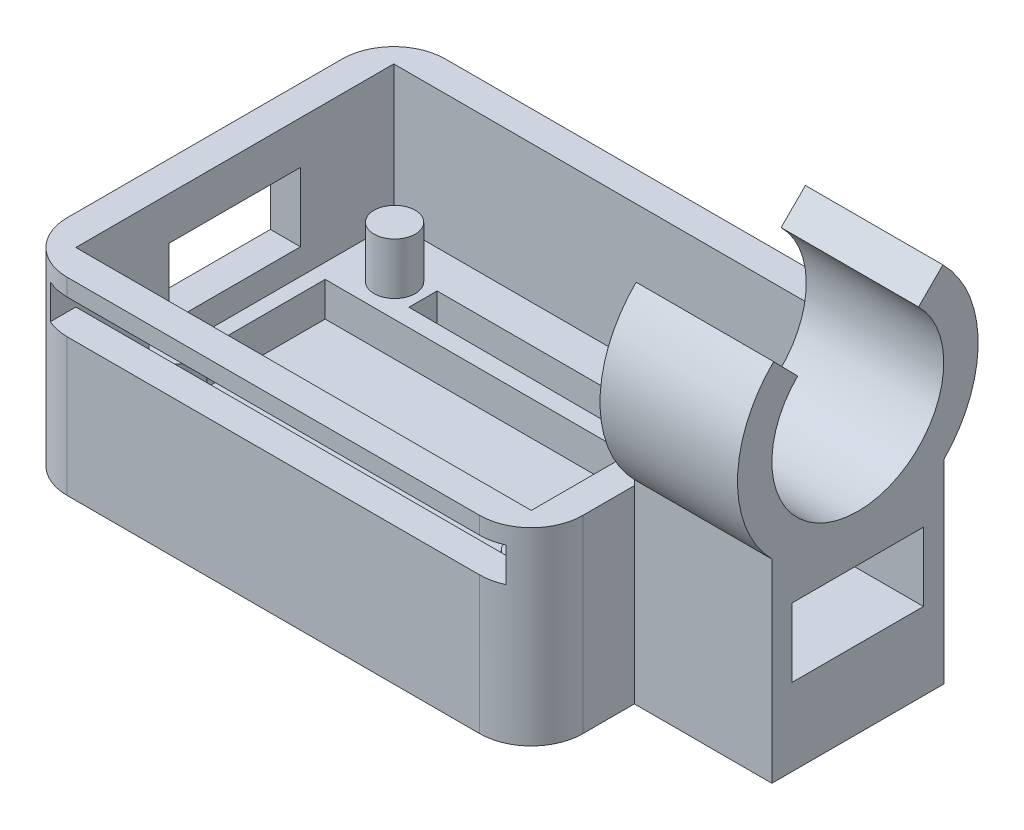
SolidWorks part; units mm, degrees
ref_plane "Front Plane" through (0, 0, 0) normal (0, 0, 1) x (1, 0, 0)
ref_plane "Top Plane" through (0, 0, 0) normal (0, 1, 0) x (1, 0, 0)
ref_plane "Right Plane" through (0, 0, 0) normal (1, 0, 0) x (0, 0, -1)
sketch "Sketch1" plane through (0, 0, 0) normal (0, 1, 0) x (1, 0, 0)
  line L1 (-15, -11) -> (15, -11)
  line L2 (-15, -11) -> (-15, 11)
  line L3 (-15, 11) -> (15, 11)
  line L4 (15, -11) -> (15, 11)
  line L5 (-15, -11) -> (15, 11) construction
  line L6 (-15, 11) -> (15, -11) construction
  point P0 (0, 0)
  dimension "D1" = 30
  dimension "D2" = 22
extrude "Boss-Extrude1" add sketch "Sketch1" along normal blind 11
sketch "Sketch2" plane through (0, 11, 0) normal (0, 1, 0) x (1, 0, 0)
  line L1 (-13.25, -9.25) -> (13.25, -9.25)
  line L2 (-13.25, -9.25) -> (-13.25, 9.25)
  line L3 (-13.25, 9.25) -> (13.25, 9.25)
  line L4 (13.25, -9.25) -> (13.25, 9.25)
  line L5 (-13.25, -9.25) -> (13.25, 9.25) construction
  line L6 (-13.25, 9.25) -> (13.25, -9.25) construction
  point P0 (0, 0)
  dimension "D1" = 26.5
  dimension "D2" = 18.5
extrude "Cut-Extrude1" cut sketch "Sketch2" against normal blind 8
sketch "Sketch3" plane through (0, 3, 0) normal (0, 1, 0) x (1, 0, 0)
  line L0 (-10.25, 6.3) -> (-10.25, 9.25) construction
  line L1 (-13.25, -6.3) -> (-10.25, -6.3) construction
  line L2 (-13.25, 9.25) -> (-13.25, -9.25) construction
  line L3 (-10.25, -6.3) -> (-10.25, -9.25) construction
  line L4 (-13.25, -9.25) -> (13.25, -9.25) construction
  line L5 (0, -6.05) -> (0, 6.05) construction
  line L6 (-6.05, 0) -> (6.05, 0) construction
  line L7 (13.25, 9.25) -> (-13.25, 9.25) construction
  line L8 (10.25, 6.3) -> (10.25, 9.25) construction
  line L9 (10.25, -6.3) -> (10.25, -9.25) construction
  line L10 (-13.25, -9.25) -> (13.25, -9.25) construction
  circle A1 centre (-10.25, -6.3) radius 1.2
  circle A2 centre (10.25, -6.3) radius 1.2
  circle A3 centre (10.25, 6.3) radius 1.2
  circle A5 centre (-10.25, 6.3) radius 1.2
  dimension "D3" = 2.4
  dimension "D4" = 2.4
  dimension "D1" = 3
  dimension "D2" = 2.95
  dimension "D5" = 2.95
extrude "Boss-Extrude2" add sketch "Sketch3" along normal blind 3
sketch "Sketch4" plane through (0, 3, 0) normal (0, 1, 0) x (1, 0, 0)
  line L5 (8.5527, 7.0707) -> (8.5527, 5.3672)
  line L6 (-9.05, 6.25) -> (-8.55, 6.25) construction
  line L7 (9.0527, 6.219) -> (8.5527, 6.219) construction
  line L10 (-8.55, 5.4293) -> (-8.55, 7.0707)
  line L11 (-8.55, 7.0707) -> (8.5527, 7.0707)
  line L12 (8.5527, 5.3672) -> (-8.55, 5.4293)
  circle A6 centre (10.25, 6.3) radius 1.2 construction
  circle A7 centre (10.25, 6.3) radius 1.2 construction
  point P17 (-8.55, 6.25)
  dimension "D1" = 0.5
  dimension "D2" = 0.5
extrude "Cut-Extrude2" cut sketch "Sketch4" against normal blind 2
mirror "Mirror1" about plane through (0, 0, 0) normal (0, 0, 1) of "Cut-Extrude2"
sketch "Sketch5" plane through (-15, 0, 0) normal (-1, 0, 0) x (0, 0, 1)
  line L0 (0, 3) -> (0, 4.5) construction
  line L1 (-9.25, 3) -> (9.25, 3) construction
  line L2 (-3.8195, 4.5) -> (3.8195, 4.5)
  line L3 (-3.8195, 4.5) -> (-3.8195, 8.5)
  line L4 (-3.8195, 8.5) -> (3.8195, 8.5)
  line L5 (3.8195, 8.5) -> (3.8195, 4.5)
  point P8 (0, 4.5)
  dimension "D1" = 4
  dimension "D2" = 1.5
extrude "Cut-Extrude3" cut sketch "Sketch5" against normal through all
sketch "Sketch6" plane through (0, 0, 11) normal (0, 0, 1) x (1, 0, 0)
  line L0 (0, 11) -> (0, 10) construction
  line L1 (-15, 11) -> (15, 11) construction
  line L2 (-13.25, 3) -> (-13.25, 11) construction
  line L3 (-13.25, 10) -> (13.25, 10)
  line L4 (-13.25, 10) -> (-13.25, 8)
  line L5 (-13.25, 8) -> (13.25, 8)
  line L6 (13.25, 10) -> (13.25, 8)
  line L7 (13.25, 3) -> (13.25, 11) construction
  dimension "D1" = 1
  dimension "D2" = 2
extrude "Cut-Extrude4" cut sketch "Sketch6" against normal up to next
sketch "Sketch8" plane through (0, 3, 0) normal (0, 1, 0) x (1, 0, 0)
  line L1 (-12.3879, -4.3961) -> (12.3879, -4.3961)
  line L2 (-12.3879, -4.3961) -> (-12.3879, 4.3961)
  line L3 (-12.3879, 4.3961) -> (12.3879, 4.3961)
  line L4 (12.3879, -4.3961) -> (12.3879, 4.3961)
  line L5 (-12.3879, -4.3961) -> (12.3879, 4.3961) construction
  line L6 (-12.3879, 4.3961) -> (12.3879, -4.3961) construction
  point P0 (0, 0)
extrude "Cut-Extrude5" cut sketch "Sketch8" against normal blind 2
fillet "Fillet1" radius 3 4 edges at (-15, 5.5, 11) (15, 5.5, 11) (15, 5.5, -11) (-15, 5.5, -11)
sketch "Sketch10" plane through (15, 0, -26) normal (-1, 0, 0) x (0, 0, 1)
  line L18 (26, 11) -> (26, 9.2) construction
  line L19 (34, 11) -> (18, 11) construction
  line L20 (26, 11.2) -> (26, 9.2) construction
  circle A0 centre (26, 16.2) radius 7
  circle A1 centre (26, 16.2) radius 5
  dimension "D3" = 10
  dimension "D4" = 14
  dimension "D1" = 1.8
  dimension "D2" = 2
extrude "Boss-Extrude4" add sketch "Sketch10" against normal blind 8 separate body
sketch "Sketch15" plane through (0, 0, 0) normal (0, 1, 0) x (1, 0, 0)
  line L1 (23, 5) -> (15, 5)
  line L2 (23, 5) -> (23, -5)
  line L3 (23, -5) -> (15, -5)
  line L4 (15, 5) -> (15, -5)
extrude "Boss-Extrude8" add sketch "Sketch15" along normal up to surface (11.301 mm away) up to face at (23, 16.2, 7)
sketch "Sketch16" plane through (23, 0, 0) normal (1, 0, 0) x (0, 0, -1)
  line L0 (0, 0) -> (0, 4.5) construction
  line L1 (-3.8195, 8.5) -> (3.8195, 8.5)
  line L2 (-3.8195, 8.5) -> (-3.8195, 4.5)
  line L3 (-3.8195, 4.5) -> (3.8195, 4.5)
  line L4 (3.8195, 8.5) -> (3.8195, 4.5)
  dimension "D1" = 4.5
extrude "Cut-Extrude7" cut sketch "Sketch16" against normal through all
sketch "Sketch17" plane through (23, 0, 0) normal (1, 0, 0) x (0, 0, -1)
  line L0 (0, 21.2) -> (0, 11.2) construction
  line L9 (0, 16.2) -> (-4.899, 21.2)
  line L10 (0, 16.2) -> (4.9497, 21.1497)
  circle A0 centre (0, 16.2) radius 5 construction
  arc A2 (5, 11.301) -> (-5, 11.301) centre (0, 16.2) ccw construction
extrude "Cut-Extrude8" cut sketch "Sketch17" against normal up to next
equation "\"`\"=19"
